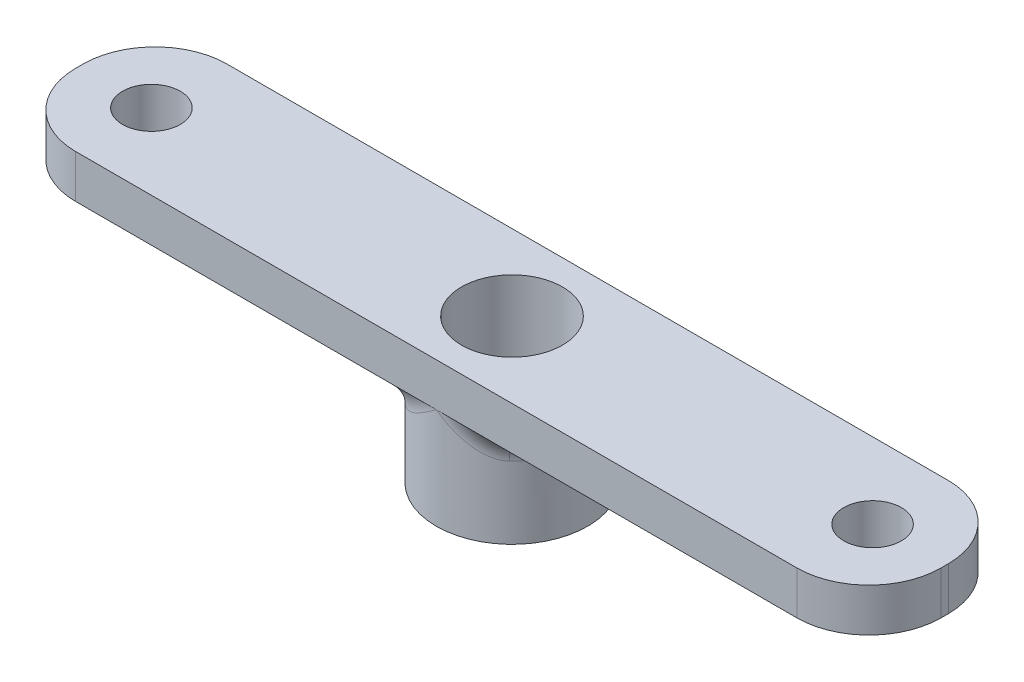
SolidWorks part; units mm, degrees
ref_plane "Front Plane" through (0, 0, 0) normal (0, 0, 1) x (1, 0, 0)
ref_plane "Top Plane" through (0, 0, 0) normal (0, 1, 0) x (1, 0, 0)
ref_plane "Right Plane" through (0, 0, 0) normal (1, 0, 0) x (0, 0, -1)
sketch "Sketch2" plane through (0, 0, 0) normal (1, 0, 0) x (0, 0, -1)
  line L0 (0, 0) -> (5.25, 0)
  line L1 (5.25, 0) -> (5.25, 7)
  line L2 (5.25, 7) -> (0, 7)
  line L3 (0, 7) -> (0, 0)
  dimension "D1" = 5.25
  dimension "D2" = 7
revolve "Revolve2" add sketch "Sketch2" angle 360 about L3
sketch "Sketch3" plane through (0, 0, 0) normal (0, -1, 0) x (1, 0, 0)
  line L0 (0, -5.25) -> (30, -5.25)
  line L1 (30, -5.25) -> (30, 5.25)
  line L2 (30, 5.25) -> (0, 5.25)
  line L3 (0, 5.25) -> (-30, 5.25)
  line L4 (-30, 5.25) -> (-30, -5.25)
  line L5 (-30, -5.25) -> (0, -5.25)
  circle A0 centre (0, 0) radius 5.25 construction
  dimension "D1" = 30
  dimension "D2" = 30
  dimension "D3" = 10.5
  dimension "D4" = 30
extrude "Boss-Extrude1" add sketch "Sketch3" against normal blind 3 from surface at -7 starting at face at (0, 7, 5.25)
fillet "Fillet4" radius 2 2 edges at (5.25, 7, 0) (-5.25, 7, 0)
fillet "Fillet7" radius 5 1 edges at (-30, 8.5, -5.25)
fillet "Fillet8" radius 5 1 edges at (-30, 8.5, 5.25)
fillet "Fillet9" radius 5 1 edges at (30, 8.5, 5.25)
fillet "Fillet10" radius 5 1 edges at (30, 8.5, -5.25)
sketch "Sketch8" plane through (0, 10, 0) normal (0, 1, 0) x (1, 0, 0)
  circle A0 centre (-25, 0) radius 2
  circle A1 centre (25, 0) radius 2
  dimension "D1" = 4
  dimension "D2" = 4
extrude "Cut-Extrude1" cut sketch "Sketch8" against normal through all
hole_wizard "Hole1" positions "Sketch9" profile "Sketch10" legacy end condition through all
sketch "Sketch9" plane through (0, 10, 0) normal (0, 1, 0) x (1, 0, 0)
  point P0 (0, 0)
sketch "Sketch10" plane through (0, 10, 0) normal (1, 0, 0) x (0, 0, 1)
  line L0 (0, 0) -> (0, 10)
  line L1 (0, 10) -> (2.5, 10)
  line L2 (2.5, 10) -> (2.5, 9)
  line L3 (2.5, 9) -> (3.5, 9)
  line L4 (3.5, 9) -> (3.5, 0)
  line L5 (3.5, 0) -> (0, 0)
  line L6 (0, 110) -> (0, -10) construction
  dimension "Diameter" = 5
  dimension "Depth" = 10
  dimension "C-Bore Diameter" = 7
  dimension "C-Bore Depth" = 9
